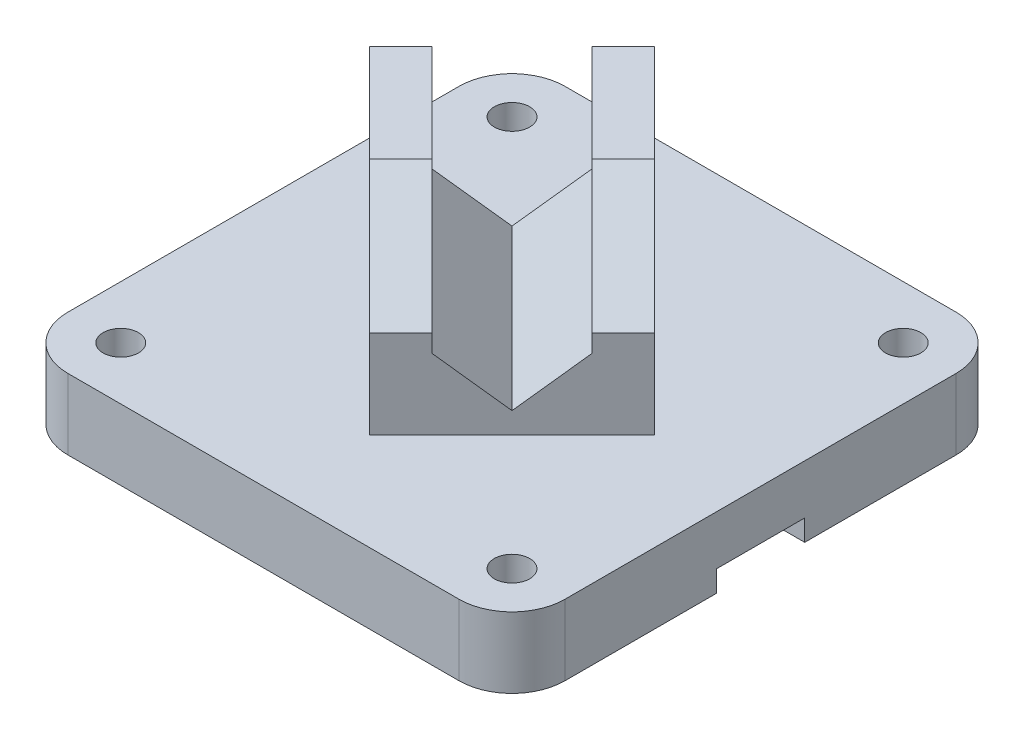
SolidWorks part; units mm, degrees
note: The reader was unsure of these and kept them because the rebuilt part matched: shared geometry of "Sketch1<3>".
ref_plane "Front Plane" through (0, 0, 0) normal (0, 0, 1) x (1, 0, 0)
ref_plane "Top Plane" through (0, 0, 0) normal (0, 1, 0) x (1, 0, 0)
ref_plane "Right Plane" through (0, 0, 0) normal (1, 0, 0) x (0, 0, -1)
sketch "Sketch1" plane through (0, 0, 0) normal (0, 1, 0) x (1, 0, 0)
  line L0 (2.4749, -42.78) -> (42.78, -2.4749)
  line L1 (-70.3918, -70.3918) -> (70.3918, -70.3918)
  line L2 (-70.3918, -70.3918) -> (-70.3918, 70.3918)
  line L3 (-70.3918, 70.3918) -> (70.3918, 70.3918)
  line L4 (70.3918, -70.3918) -> (70.3918, 70.3918)
  line L5 (-70.3918, -70.3918) -> (70.3918, 70.3918) construction
  line L6 (-70.3918, 70.3918) -> (70.3918, -70.3918) construction
  line L7 (2.4749, -42.78) -> (-42.78, 2.4749)
  line L8 (42.78, -2.4749) -> (-2.4749, 42.78)
  line L9 (-42.78, 2.4749) -> (-2.4749, 42.78)
  line L10 (-47.2797, 0) -> (50.3918, 0) construction
  circle A0 centre (55.3918, 55.3918) radius 5
  arc A1 (70.3918, 55.3918) -> (55.3918, 70.3918) centre (55.3918, 55.3918) ccw
  arc A2 (-55.3918, -70.3918) -> (-70.3918, -55.3918) centre (-55.3918, -55.3918) cw
  circle A3 centre (-55.3918, -55.3918) radius 5
  circle A4 centre (-55.3918, 55.3918) radius 5
  arc A5 (-55.3918, 70.3918) -> (-70.3918, 55.3918) centre (-55.3918, 55.3918) ccw
  arc A6 (70.3918, -55.3918) -> (55.3918, -70.3918) centre (55.3918, -55.3918) cw
  circle A7 centre (55.3918, -55.3918) radius 5
  point P0 (0, 0)
  dimension "D1" = 45
  dimension "D5" = 10
  dimension "D6" = 30
  dimension "D2" = 140.7835
  dimension "D3" = 57
  dimension "D4" = 64
extrude "Boss-Extrude1" add sketch "Sketch1" along normal blind 20 contours A6 L4 A1 L3 A5 L2 A2 L1 A3 A0 L7 L9 L8 L0 A4 A7
extrude "Boss-Extrude2" add sketch "Sketch1<3>" along normal blind 70 contours L9 L7 L0 L8
sketch "Sketch1<3>" plane through (0, 0, 0) normal (0, 1, 0) x (1, 0, 0) same geometry as "Sketch1"
sketch "Sketch2" plane through (20.1525, 0, -20.1525) normal (0.7071, 0, -0.7071) x (-0.7071, 0, -0.7071)
  line L0 (-32, 70) -> (-32, 20) construction
  line L2 (88.9424, 20) -> (10.6066, 20) construction
  circle A0 centre (0, 52) radius 8
  dimension "D1" = 16
  dimension "D3" = 32
  dimension "D2" = 32
extrude "Cut-Extrude1" cut sketch "Sketch2" against normal through all both and the other way through all
sketch "Sketch3" plane through (22.6274, 0, 22.6274) normal (0.7071, 0, 0.7071) x (0.7071, 0, -0.7071)
  line L0 (16, 70) -> (16, 40)
  line L1 (-28.5, 70) -> (28.5, 70) construction
  line L2 (16, 40) -> (0, 26)
  line L3 (0, 26) -> (-16, 40)
  line L4 (-16, 40) -> (-16, 70)
  line L5 (0, 71.992) -> (0, 67.2566) construction
  line L6 (10.6066, 20) -> (88.9424, 20) construction
  line L7 (10.6066, 20) -> (-10.6066, 20) construction
  dimension "D1" = 32
  dimension "D2" = 20
  dimension "D3" = 6
extrude "Cut-Extrude2" cut sketch "Sketch3" against normal through all
chamfer "Chamfer1" distance 25 angle 45 2 edges at (6.8943, 70, 38.3605) (38.3605, 70, 6.8943)
sketch "Sketch4" plane through (70.3918, 0, 0) normal (1, 0, 0) x (0, 0, -1)
  line L1 (-12.5, -6) -> (12.5, -6)
  line L2 (-12.5, -6) -> (-12.5, 6)
  line L3 (-12.5, 6) -> (12.5, 6)
  line L4 (12.5, -6) -> (12.5, 6)
  line L5 (-12.5, -6) -> (12.5, 6) construction
  line L6 (-12.5, 6) -> (12.5, -6) construction
  point P0 (0, 0)
  dimension "D1" = 12
  dimension "D2" = 25
extrude "Cut-Extrude3" cut sketch "Sketch4" against normal up to next
